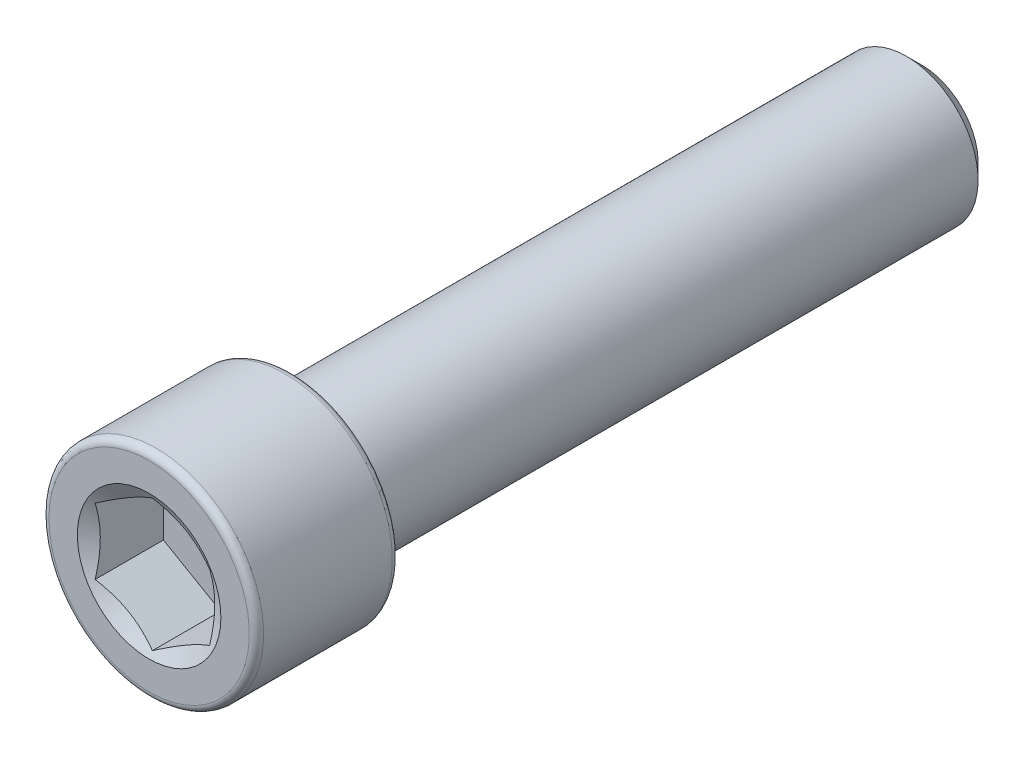
SolidWorks part; units mm, degrees
ref_plane "Front Plane" through (0, 0, 0) normal (0, 0, 1) x (1, 0, 0)
ref_plane "Top Plane" through (0, 0, 0) normal (0, 1, 0) x (1, 0, 0)
ref_plane "Right Plane" through (0, 0, 0) normal (1, 0, 0) x (0, 0, -1)
sketch "Sketch1" plane through (0, 0, 0) normal (1, 0, 0) x (0, 0, -1)
  line L0 (21.4312, 0) -> (-21.4312, 0) construction
  line L1 (-13.4938, 5.9531) -> (-13.4937, -5.9531) construction
  line L2 (21.4313, 3.9688) -> (21.4313, -3.9687) construction
  line L3 (21.3431, 4.1215) -> (22.0486, 2.8994) construction
  line L4 (21.9604, 3.0522) -> (22.1368, 3.0522) construction
  line L5 (22.0486, 2.8994) -> (22.7542, 4.1215) construction
  line L6 (22.7542, 4.1215) -> (21.3431, 4.1215) construction
  line L7 (22.0486, 3.0522) -> (22.0486, 2.8994) construction
  line L8 (22.0486, 4.1215) -> (22.0486, 3.9688) construction
  line L9 (22.666, 3.9688) -> (21.4313, 3.9688) construction
  point P4 (-13.4937, 0)
  point P6 (-13.4937, 3.175)
  point P7 (17.9035, -3.9687)
  point P20 (22.0486, 4.0451)
  dimension "Head Height" = 7.9375
  dimension "Head Diameter" = 11.9062
  dimension "Drive Size" = 6.35
  dimension "Length" = 34.925
  dimension "Screw Size Decimal Equivalent" = 7.9375
  dimension "Pitch" = 1.4111
  dimension "Pitch/8" = 0.1764
  dimension "Thread Note" = 3.5278
sketch "Sketch2" plane through (0, 0, 0) normal (1, 0, 0) x (0, 0, -1)
  line L0 (21.4312, 0) -> (21.4313, 3.1221)
  line L1 (21.4313, 3.9688) -> (21.4313, -3.9687) construction
  line L2 (21.4313, 3.1221) -> (20.5846, 3.9688)
  line L3 (20.5846, 3.9688) -> (-13.4938, 3.9687)
  line L4 (-13.4938, 3.9687) -> (-13.4937, 5.5562)
  line L5 (-13.8906, 5.9531) -> (-21.0344, 5.9531)
  line L6 (-21.4312, 5.5562) -> (-21.4312, 0)
  line L7 (21.4312, 0) -> (-21.4312, 0) construction
  line L8 (-21.4312, 0) -> (21.4312, 0)
  arc A0 (-13.4937, 5.5562) -> (-13.8906, 5.9531) centre (-13.8906, 5.5562) ccw
  arc A1 (-21.0344, 5.9531) -> (-21.4312, 5.5562) centre (-21.0344, 5.5562) ccw
  point P19 (-13.4938, 5.9531)
  dimension "D3" = 0.3969
  dimension "D1" = 0.8467
  dimension "D2" = 45
revolve "Revolve1" add sketch "Sketch2" angle 360 about L0
sketch "Sketch3" plane through (0, 0, 0) normal (0, 0, 1) x (1, 0, 0)
  line L1 (-3.175, 1.8331) -> (-3.175, -1.8331)
  line L2 (-3.175, -1.8331) -> (0, -3.6662)
  line L3 (0, -3.6662) -> (3.175, -1.8331)
  line L4 (3.175, -1.8331) -> (3.175, 1.8331)
  line L5 (3.175, 1.8331) -> (0, 3.6662)
  line L6 (0, 3.6662) -> (-3.175, 1.8331)
  circle A0 centre (0, 0) radius 3.175 construction
  circle A1 centre (0, 0) radius 5.9531 construction
extrude "Cut-Extrude1" cut sketch "Sketch3" against normal blind 3.9688 from vertex starting at point (0, 0, 21.4312)
sketch "Sketch4" plane through (0, 0, 21.4312) normal (0, 0, 1) x (1, 0, 0)
  line L0 (0, 3.6662) -> (0, 4.2962) construction
  line L1 (0, 4.2962) -> (0, 4.9262) construction
  line L2 (0, 4.9262) -> (0, 5.5562) construction
  circle A0 centre (0, 0) radius 3.9812
  point P12 (0, 3.9812)
extrude "Cut-Extrude2" cut sketch "Sketch4" against normal through all draft 60
split "Split1" [suppressed] bodies to split 106 112
sketch "Sketch5" [suppressed] plane through (0, 0, 0) normal (1, 0, 0) x (0, 0, -1)
  line L0 (21.9604, 3.0522) -> (22.1368, 3.0522)
  line L1 (22.1368, 3.0522) -> (22.7101, 4.0451)
  line L2 (22.7101, 4.0451) -> (21.3872, 4.0451)
  line L3 (21.3872, 4.0451) -> (21.9604, 3.0522)
  line L4 (21.3431, 4.1215) -> (22.0486, 2.8994) construction
sketch "Sketch6" [suppressed] plane through (0, 0, -21.4313) normal (0, 0, -1) x (-1, 0, 0)
  circle A0 centre (0, 0) radius 3.9687
curve "Helix/Spiral1" [suppressed] pitch 1.4111 height 36.3361 turns 25.75
sweep "Cut-Sweep1" [suppressed] cut profiles "Sketch5" path "Helix/Spiral1"
sketch "Sketch7" [suppressed] plane through (0, 0, 13.4937) normal (0, 0, -1) x (-1, 0, 0)
  circle A0 centre (0, 0) radius 4.0195
  circle A1 centre (0, 0) radius 3.9687 construction
  dimension "D1" = 0.0508
extrude "Boss-Extrude1" [suppressed] add sketch "Sketch7" along normal blind 4.2333 draft 20 and the other way blind 0.7937
ref_plane "Plane1" [suppressed] through (0, 0, 16.1131) normal (0, 0, -1) x (-1, 0, 0)
sketch "Sketch13" [suppressed] plane through (0, 0, 16.1131) normal (0, 0, -1) x (-1, 0, 0)
  line L0 (0.1488, 5.9513) -> (0, 0) construction
  line L1 (0, 0) -> (-0.1488, 5.9513) construction
  line L3 (0.1464, 5.853) -> (0.1488, 5.9513)
  line L6 (-0.1464, 5.853) -> (-0.1488, 5.9513)
  arc A1 (0.1488, 5.9513) -> (-0.1488, 5.9513) centre (0, 0) ccw
  circle A2 centre (0, 0) radius 5.9531 construction
  arc A3 (0.1464, 5.853) -> (-0.1464, 5.853) centre (0, 0) ccw
  point P2 (0, 5.9531)
  dimension "D3" = 0.0982
  dimension "D1" = 0.2977
extrude "Cut-Extrude3" [suppressed] cut sketch "Sketch13" against normal blind 4.4291
chamfer "Chamfer3" [suppressed] distance 0.0982 angle 60
chamfer "Chamfer4" [suppressed] distance 0.0982 angle 85
pattern_circular "CirPattern2" [suppressed] count 50 over 360 about axis through (0, 0, -21.4312) along (0, 0, 1) of bodies 134
equation "\"Pitch/8@Sketch1\" = \"Pitch@Sketch1\" / 8"
equation "\"Thread Note@Sketch1\"=\"Pitch@Sketch1\" * 2.5"
equation "\"D1@Sketch2\"=\"Pitch@Sketch1\"*.60"
equation "\"D3@Sketch2\"=\"Head Height@Sketch1\"*.05"
equation "\"D1@Cut-Extrude1\" = \"Head Height@Sketch1\" * .5"
equation "\"D3@Helix/Spiral1\" = \"Length@Sketch1\" + \"Pitch@Sketch1\""
equation "\"D4@Helix/Spiral1\" = \"Pitch@Sketch1\""
equation "\"D2@Boss-Extrude1\" = \"Head Height@Sketch1\" * .1"
equation "\"D1\"= \"Screw Size Decimal Equivalent@Sketch1\" * .4"
equation "\"D1@Plane1\"=\"Head Height@Sketch1\" * .33"
equation "\"D1@Cut-Extrude3\"=( \"Head Height@Sketch1\" - \"D1@Plane1\" - \"D3@Sketch2\" )  * .9"
equation "\"D1@Chamfer3\"=\"D3@Sketch13\""
equation "\"D1@Chamfer4\"=\"D3@Sketch13\""
equation "\"D1@CirPattern2\"=( \"Head Diameter@Sketch1\" * pi )  /  ( 2.5*\"D1@Sketch13\" )"
equation "\"D1@Sketch13\"=\"Head Diameter@Sketch1\" * .025"
equation "\"D3@Sketch13\"=\"D1@Sketch13\"*.33"
equation "\"D1@Boss-Extrude1\"=\"Pitch@Sketch1\"*3"
